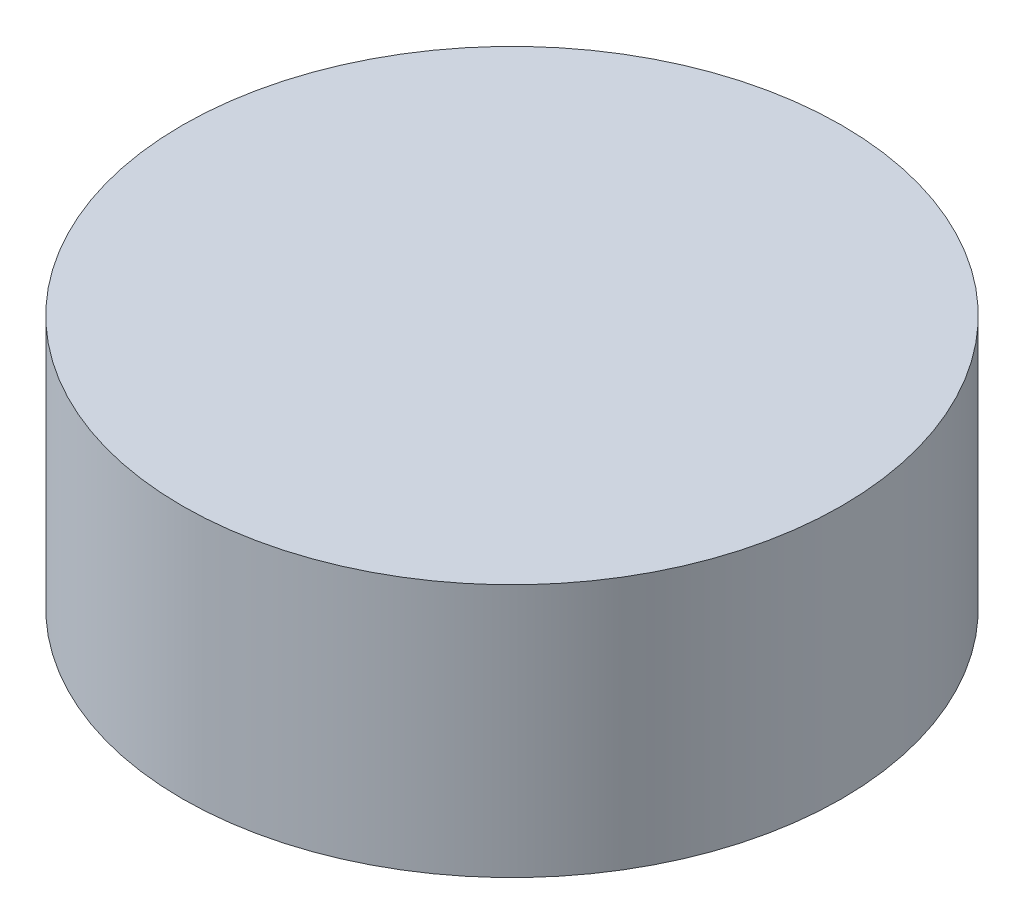
SolidWorks part; units mm, degrees
ref_plane "Спереди" through (0, 0, 0) normal (0, 0, 1) x (1, 0, 0)
ref_plane "Сверху" through (0, 0, 0) normal (0, 1, 0) x (1, 0, 0)
ref_plane "Справа" through (0, 0, 0) normal (1, 0, 0) x (0, 0, -1)
sketch "Эскиз1" plane through (0, 0, 0) normal (0, 1, 0) x (1, 0, 0)
  circle A0 centre (0, 0) radius 32.5
extrude "abot_left_wheel" add sketch "Эскиз1" along normal blind 25
ref_axis "AXIS_LEFT_WHEEL" through (0, 25, 0) along (0, -1, 0)
